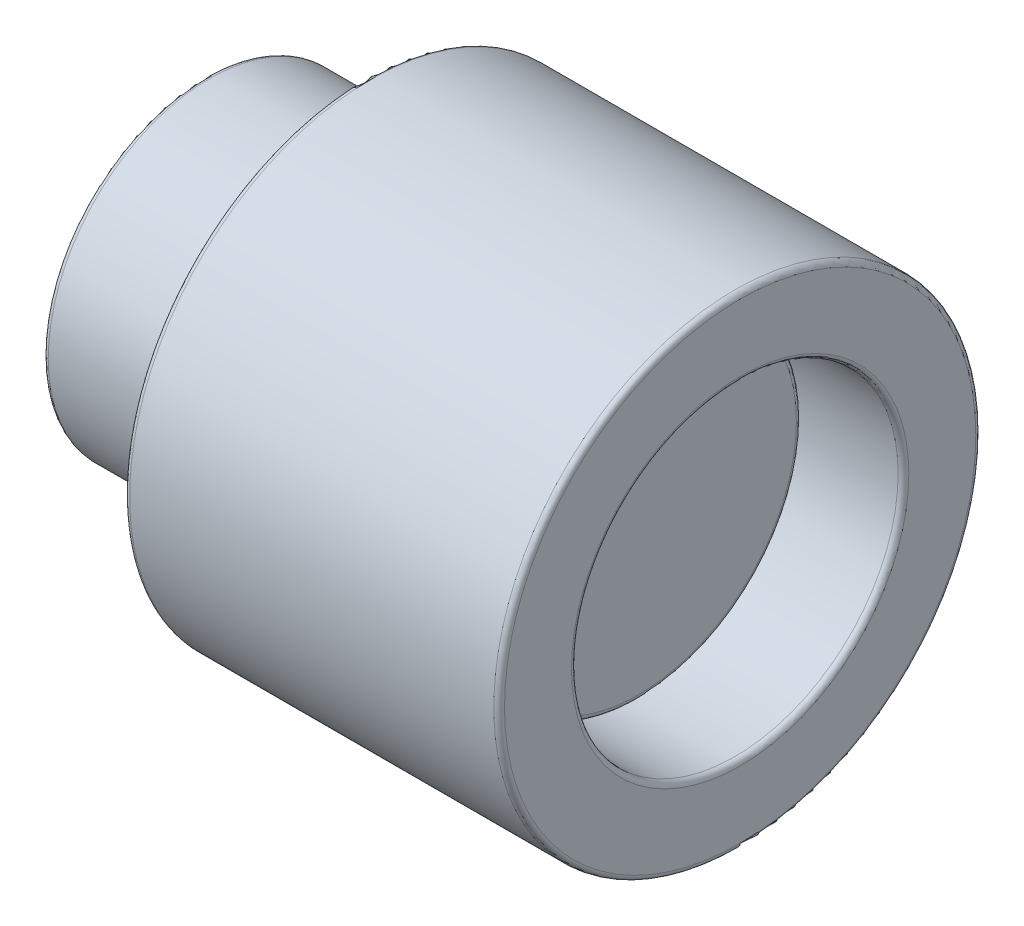
SolidWorks part; units mm, degrees
ref_plane "前视基准面" through (0, 0, 0) normal (0, 0, 1) x (1, 0, 0)
ref_plane "上视基准面" through (0, 0, 0) normal (0, 1, 0) x (1, 0, 0)
ref_plane "右视基准面" through (0, 0, 0) normal (1, 0, 0) x (0, 0, -1)
other "Configuration Table"
sketch "草图1" plane through (0, 0, 0) normal (1, 0, 0) x (0, 0, -1)
  circle A0 centre (0, 0) radius 4.5
  circle A1 centre (0, 0) radius 3.05
  dimension "D1" = 6.1
  dimension "D2" = 9
extrude "凸台-拉伸1" add sketch "草图1" along normal blind 7
sketch "草图2" plane through (0, 0, 0) normal (-1, 0, 0) x (0, 0, 1)
  circle A0 centre (0, 0) radius 3.05
  dimension "D1" = 6.1
extrude "凸台-拉伸2" add sketch "草图2" along normal blind 3 and the other way offset from surface (5.1 mm away) 1.9 separate body other way up to face at (7, 0, -4.5)
sketch "草图3" plane through (-3, 0, 0) normal (-1, 0, 0) x (0, 0, 1)
  circle A0 centre (0, 0) radius 3.02
  circle A1 centre (0, 0) radius 3.05
  circle A2 centre (0, 0) radius 3.05
  dimension "D1" = 0
  dimension "D2" = 0.03
extrude "切除-拉伸1" cut sketch "草图3" against normal up to surface (3 mm away) up to face at (0, 0, -4.5)
fillet "圆角1" radius 0.1 3 edges at (7, 0, -3.05) (0, 0, -4.5) (7, 0, -4.5)
fillet "圆角2" radius 0.1 1 edges at (-3, 0, 3.02)
fillet "圆角3" radius 0.1 1 edges at (0, 0, -3.02)
fillet "圆角4" radius 0.1 1 edges at (5.1, 0, -3.05)
